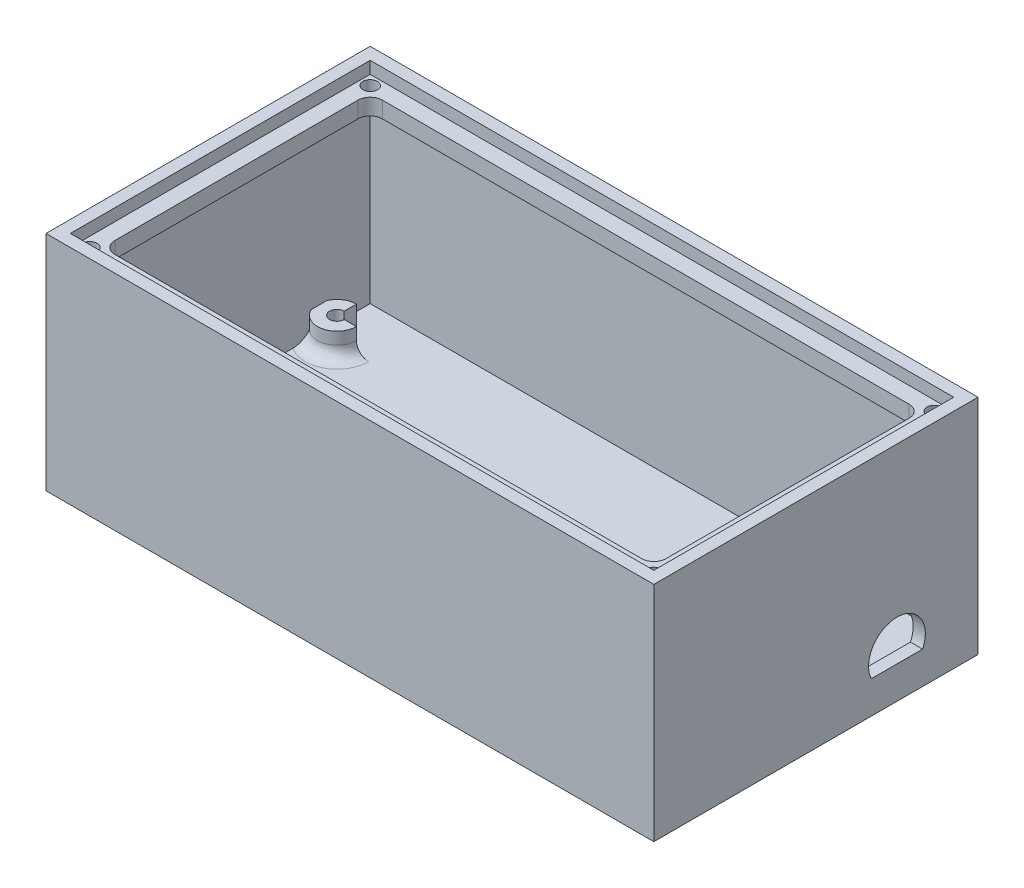
SolidWorks part; units mm, degrees
ref_plane "Front Plane" through (0, 0, 0) normal (0, 0, 1) x (1, 0, 0)
ref_plane "Top Plane" through (0, 0, 0) normal (0, 1, 0) x (1, 0, 0)
ref_plane "Right Plane" through (0, 0, 0) normal (1, 0, 0) x (0, 0, -1)
sketch "Sketch1" plane through (0, 0, 0) normal (0, 1, 0) x (1, 0, 0)
  line L1 (0, 0) -> (75, 0)
  line L2 (0, 0) -> (0, 40)
  line L3 (0, 40) -> (75, 40)
  line L4 (75, 0) -> (75, 40)
  dimension "D1" = 75
  dimension "D2" = 40
extrude "Boss-Extrude1" add sketch "Sketch1" along normal blind 1.5
sketch "Sketch2" plane through (0, 1.5, 0) normal (0, 1, 0) x (1, 0, 0)
  line L0 (1.5, 38.5) -> (1.5, 1.5)
  line L1 (0, 40) -> (75, 40)
  line L2 (0, 40) -> (0, 0)
  line L3 (0, 0) -> (75, 0)
  line L4 (75, 40) -> (75, 0)
  line L5 (1.5, 1.5) -> (73.5, 1.5)
  line L6 (73.5, 38.5) -> (73.5, 1.5)
  line L7 (1.5, 38.5) -> (73.5, 38.5)
  dimension "D1" = 1.5
extrude "Boss-Extrude2" add sketch "Sketch2" along normal blind 26
sketch "Sketch3" plane through (0, 0, 0) normal (-1, 0, 0) x (0, 0, 1)
  line L0 (-40, 1.5) -> (0, 1.5) construction
  line L1 (-40, 27.5) -> (-40, 0) construction
  line L2 (0, 27.5) -> (0, 0) construction
  line L3 (-40, 0) -> (0, 0) construction
  line L5 (-24.5, 1.5) -> (-15.5, 1.5)
  line L6 (-24.5, 1.5) -> (-24.5, 5)
  line L7 (-24.5, 5) -> (-15.5, 5)
  line L8 (-15.5, 1.5) -> (-15.5, 5)
  dimension "D1" = 1.5
  dimension "D2" = 9
  dimension "D3" = 3.5
  dimension "D4" = 15.5
  dimension "D5" = 15.5
extrude "Cut-Extrude1" cut sketch "Sketch3" against normal blind 25
fillet "Fillet1" radius 1 2 edges at (0.75, 5, -24.5) (0.75, 5, -15.5)
sketch "Sketch4" plane through (0, 1.5, 0) normal (0, 1, 0) x (1, 0, 0)
  line L0 (1.5, 20) -> (73.5, 20) construction
  line L1 (1.5, 38.5) -> (1.5, 1.5) construction
  line L2 (73.5, 1.5) -> (73.5, 38.5) construction
  line L3 (1.5, 38.5) -> (1.5, 24.5) construction
  line L4 (1.7, 34.2) -> (56.6, 34.2) construction
  line L5 (1.7, 34.2) -> (1.7, 5.8) construction
  line L6 (1.7, 5.8) -> (56.6, 5.8) construction
  line L7 (56.6, 34.2) -> (56.6, 5.8) construction
  line L8 (4.6, 32.2) -> (6.1, 32.2)
  line L9 (3.7, 33.1) -> (3.7, 34.6)
  line L10 (54.6, 33.1) -> (54.6, 34.6)
  line L11 (3.7, 6.9) -> (3.7, 5.4)
  line L12 (4.6, 7.8) -> (6.1, 7.8)
  line L13 (54.6, 6.9) -> (54.6, 5.4)
  line L14 (52.2, 32.2) -> (53.7, 32.2)
  line L15 (52.2, 7.8) -> (53.7, 7.8)
  arc A0 (3.7, 33.1) -> (4.6, 32.2) centre (3.7, 32.2) ccw
  arc A1 (4.6, 7.8) -> (3.7, 6.9) centre (3.7, 7.8) ccw
  arc A2 (54.6, 6.9) -> (53.7, 7.8) centre (54.6, 7.8) ccw
  arc A3 (53.7, 32.2) -> (54.6, 33.1) centre (54.6, 32.2) ccw
  arc A4 (3.7, 34.6) -> (6.1, 32.2) centre (3.7, 32.2) ccw
  arc A5 (6.1, 7.8) -> (3.7, 5.4) centre (3.7, 7.8) ccw
  arc A6 (54.6, 5.4) -> (52.2, 7.8) centre (54.6, 7.8) ccw
  arc A7 (52.2, 32.2) -> (54.6, 34.6) centre (54.6, 32.2) ccw
  circle A9 centre (3.7, 32.2) radius 0.9 construction
  circle A10 centre (3.7, 32.2) radius 2.4 construction
  circle A11 centre (54.6, 32.2) radius 2.4 construction
  circle A12 centre (54.6, 32.2) radius 0.9 construction
  circle A13 centre (54.6, 7.8) radius 2.4 construction
  circle A14 centre (3.7, 7.8) radius 2.4 construction
  circle A15 centre (3.7, 7.8) radius 0.9 construction
  circle A16 centre (54.6, 7.8) radius 0.9 construction
  point P11 (6.1, 32.2)
  point P13 (55.4607, 8.0631)
  point P25 (6.1, 7.8)
  point P27 (55.4607, 32.4631)
  point P34 (4.5607, 32.4631)
  point P38 (57, 32.2)
  point P44 (57, 7.8)
  point P48 (4.5607, 8.0631)
  dimension "D3" = 2
  dimension "D1" = 54.9
  dimension "D2" = 28.4
  dimension "D4" = 2
  dimension "D5" = 2
  dimension "D6" = 2
  dimension "D7" = 2
  dimension "D8" = 2
  dimension "D9" = 2
  dimension "D10" = 2
  dimension "D11" = 14.2
  dimension "D12" = 0.2
  dimension "D13" = 1.5
extrude "Boss-Extrude3" add sketch "Sketch4" along normal blind 3
fillet "Fillet2" radius 1.5 4 edges at (56.2971, 1.5, -9.4971) (56.2971, 1.5, -30.5029) (4.1899, 1.5, -10.1495) (4.1899, 1.5, -29.8505)
sketch "Sketch5" plane through (75, 0, 0) normal (1, 0, 0) x (0, 0, -1)
  line L0 (40, 27.5) -> (40, 0) construction
  line L2 (0, 0) -> (40, 0) construction
  line L5 (0, 4) -> (40, 4)
  line L6 (26.8377, 4) -> (33.1623, 4)
  arc A0 (33.1623, 4) -> (26.8377, 4) centre (30, 5.5) ccw
  dimension "D1" = 5.5
  dimension "D3" = 4
  dimension "D2" = 10
extrude "Cut-Extrude2" cut sketch "Sketch5" against normal blind 3
sketch "Sketch6" plane through (0, 27.5, 0) normal (0, 1, 0) x (1, 0, 0)
  line L0 (3.5, 36.5) -> (3.5, 3.5)
  line L1 (0, 40) -> (75, 40)
  line L2 (0, 40) -> (0, 0)
  line L3 (0, 0) -> (75, 0)
  line L4 (75, 40) -> (75, 0)
  line L5 (3.5, 3.5) -> (71.5, 3.5)
  line L6 (71.5, 36.5) -> (71.5, 3.5)
  line L7 (3.5, 36.5) -> (71.5, 36.5)
  dimension "D2" = 68
  dimension "D1" = 3.5
extrude "Boss-Extrude4" add sketch "Sketch6" along normal blind 2 from offset 3.5 offset against normal yes
fillet "Fillet3" radius 1.5 8 edges at (1.5, 24, -20) (37.5, 24, -1.5) (73.5, 24, -20) (37.5, 24, -38.5) (71.5, 25, -3.5) (71.5, 25, -36.5) (3.5, 25, -3.5) (3.5, 25, -36.5)
sketch "Sketch9" plane through (0, 26, 0) normal (0, 1, 0) x (1, 0, 0)
  line L0 (1.5, 1.5) -> (3.9393, 3.9393) construction
  line L1 (1.5, 38.5) -> (3.9393, 36.0607) construction
  line L2 (73.5, 38.5) -> (71.0607, 36.0607) construction
  line L3 (73.5, 1.5) -> (71.0607, 3.9393) construction
  line L4 (1.5, 1.5) -> (73.5, 1.5) construction
  line L6 (73.5, 1.5) -> (73.5, 38.5) construction
  line L7 (73.5, 38.5) -> (1.5, 38.5) construction
  line L8 (1.5, 38.5) -> (1.5, 1.5) construction
  line L9 (1.5, 1.5) -> (73.5, 1.5) construction
  circle A0 centre (2.7, 37.3) radius 0.9
  circle A1 centre (2.7, 2.7) radius 0.9
  circle A2 centre (72.3, 2.7) radius 0.9
  circle A3 centre (72.3, 37.3) radius 0.9
  arc A4 (3.5, 5) -> (5, 3.5) centre (5, 5) ccw construction
  arc A5 (5, 36.5) -> (3.5, 35) centre (5, 35) ccw construction
  arc A6 (71.5, 35) -> (70, 36.5) centre (70, 35) ccw construction
  arc A7 (70, 3.5) -> (71.5, 5) centre (70, 5) ccw construction
  point P44 (3.324, 38.5)
  dimension "D1" = 1.2
  dimension "D2" = 1.2
  dimension "D3" = 1.2
  dimension "D4" = 1.2
  dimension "D5" = 1.2
  dimension "D6" = 1.2
  dimension "D7" = 1.2
  dimension "D8" = 1.2
extrude "Cut-Extrude3" cut sketch "Sketch9" against normal blind 4
